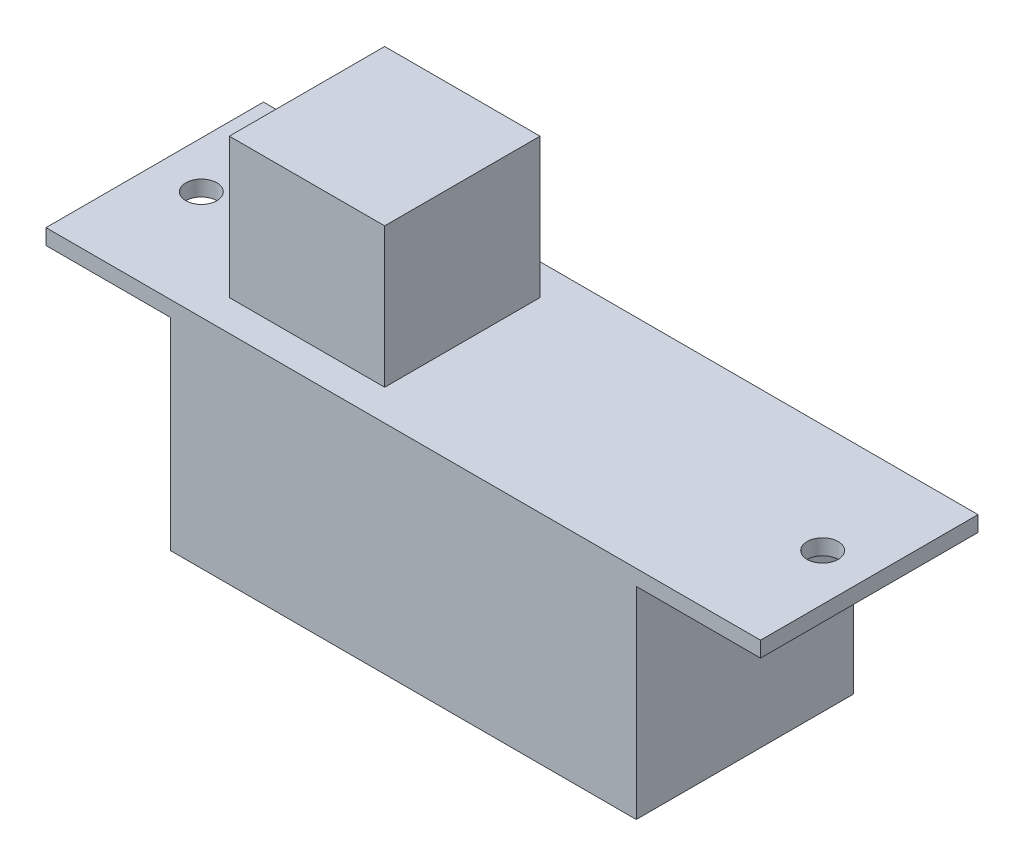
SolidWorks part; units mm, degrees
ref_plane "Front Plane" through (0, 0, 0) normal (0, 0, 1) x (1, 0, 0)
ref_plane "Top Plane" through (0, 0, 0) normal (0, 1, 0) x (1, 0, 0)
ref_plane "Right Plane" through (0, 0, 0) normal (1, 0, 0) x (0, 0, -1)
sketch "Sketch1" plane through (0, 0, 0) normal (0, 1, 0) x (1, 0, 0)
  line L1 (-7.5, -3.5) -> (7.5, -3.5)
  line L2 (-7.5, -3.5) -> (-7.5, 3.5)
  line L3 (-7.5, 3.5) -> (7.5, 3.5)
  line L4 (7.5, -3.5) -> (7.5, 3.5)
  line L5 (-7.5, -3.5) -> (7.5, 3.5) construction
  line L6 (-7.5, 3.5) -> (7.5, -3.5) construction
  point P0 (0, 0)
  dimension "D1" = 15
  dimension "D2" = 7
extrude "Boss-Extrude1" add sketch "Sketch1" along normal blind 7
sketch "Sketch2" plane through (0, 7, 0) normal (0, 1, 0) x (1, 0, 0)
  line L0 (7.5, 3.5) -> (-7.5, 3.5) construction
  line L1 (-11.5, -3.5) -> (11.5, -3.5)
  line L2 (-11.5, -3.5) -> (-11.5, 3.5)
  line L3 (-11.5, 3.5) -> (11.5, 3.5)
  line L4 (11.5, -3.5) -> (11.5, 3.5)
  line L5 (-11.5, -3.5) -> (11.5, 3.5) construction
  line L6 (-11.5, 3.5) -> (11.5, -3.5) construction
  line L7 (-10, 0) -> (-7.5, 0) construction
  line L8 (-7.5, 3.5) -> (-7.5, -3.5) construction
  line L9 (-7.5, 0) -> (7.5, 0) construction
  line L11 (7.5, -3.5) -> (7.5, 3.5) construction
  line L13 (7.5, 0) -> (10, 0) construction
  line L14 (10, 0) -> (11.5, 0) construction
  line L15 (-10, 0) -> (-11.5, 0) construction
  circle A0 centre (-10, 0) radius 0.5
  circle A1 centre (10, 0) radius 0.5
  point P0 (0, 0)
  point P11 (0, 0)
  dimension "D2" = 1
  dimension "D1" = 20
  dimension "D3" = 1.5
  dimension "D4" = 1.5
  dimension "D5" = 23
extrude "Boss-Extrude2" add sketch "Sketch2" against normal blind 0.5
sketch "Sketch3" plane through (0, 7, 0) normal (0, 1, 0) x (1, 0, 0)
  line L0 (0, 0) -> (-11.5, 0) construction
  line L1 (-11.5, 3.5) -> (-11.5, -3.5) construction
  line L3 (-1.5989, -2.5) -> (-6.5989, -2.5)
  line L4 (-1.5989, -2.5) -> (-1.5989, 2.5)
  line L5 (-1.5989, 2.5) -> (-6.5989, 2.5)
  line L6 (-6.5989, -2.5) -> (-6.5989, 2.5)
  line L7 (-1.5989, -2.5) -> (-6.5989, 2.5) construction
  line L8 (-1.5989, 2.5) -> (-6.5989, -2.5) construction
  line L12 (7.5, -3.5) -> (7.5, 3.5)
  line L13 (-7.5, -3.5) -> (7.5, -3.5)
  line L14 (-7.5, 3.5) -> (-7.5, -3.5)
  line L15 (7.5, 3.5) -> (-7.5, 3.5)
  line L16 (7.5, -3.5) -> (7.5, 3.5) construction
  line L17 (-7.5, -3.5) -> (7.5, -3.5) construction
  line L18 (-7.5, 3.5) -> (-7.5, -3.5) construction
  line L19 (7.5, 3.5) -> (-7.5, 3.5) construction
  point P5 (-4.0989, 0)
  point P10 (-4.6865, 2.9352)
  point P11 (-3.7261, 0)
  point P14 (-4.0989, 0)
  dimension "D2" = 5
  dimension "D1" = 0
extrude "Boss-Extrude3" add sketch "Sketch3" along normal blind 4.5
